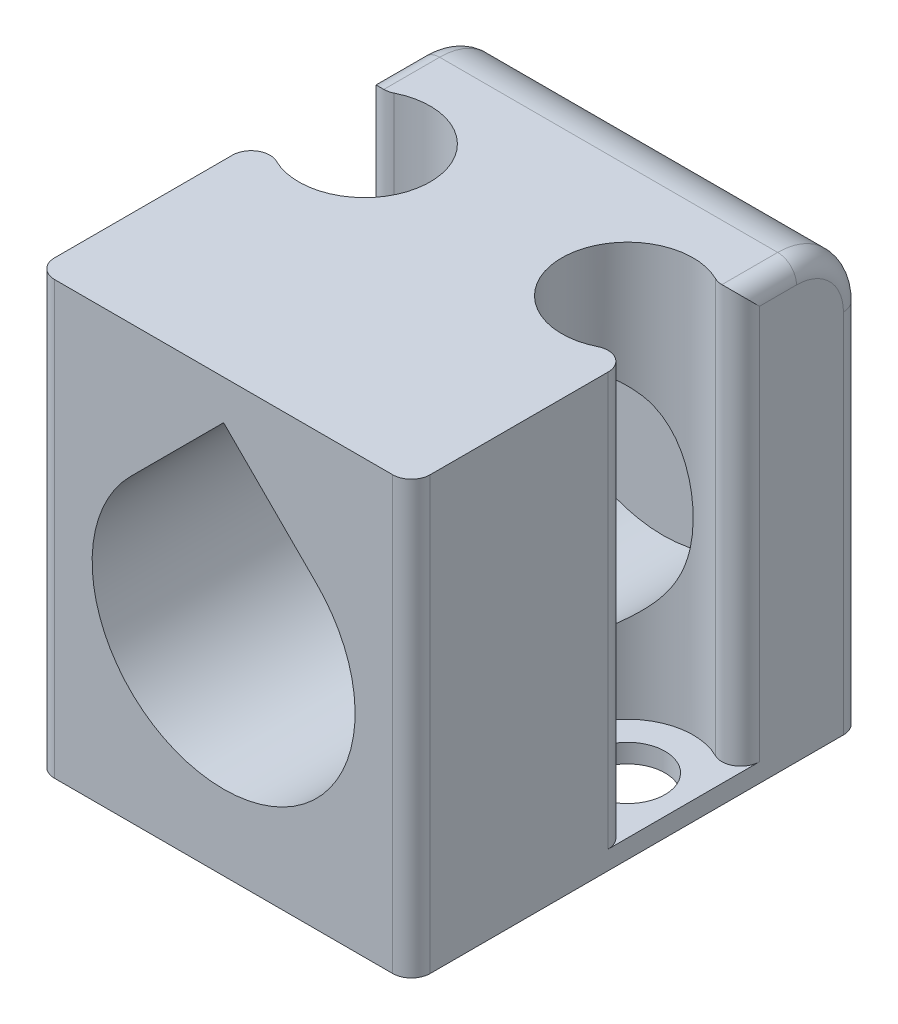
SolidWorks part; units mm, degrees
ref_plane "Front" through (0, 0, 0) normal (0, 0, 1) x (1, 0, 0)
ref_plane "Top" through (0, 0, 0) normal (0, 1, 0) x (1, 0, 0)
ref_plane "Right" through (0, 0, 0) normal (1, 0, 0) x (0, 0, -1)
other "Configuration Table"
sketch "Sketch1" plane through (0, 0, 0) normal (0, 1, 0) x (1, 0, 0)
  line L0 (0, 20.5519) -> (0, -18.8766) construction
  line L1 (-12.5093, 0) -> (15.4681, 0) construction
  line L2 (-10, 7.5) -> (10, 7.5)
  line L3 (-10, 7.5) -> (-10, -16.5)
  line L4 (-10, -16.5) -> (10, -16.5)
  line L5 (10, 7.5) -> (10, -16.5)
  circle A0 centre (-7, -2) radius 2
  circle A1 centre (7, -2) radius 2
  circle A2 centre (-7, -2) radius 3.5
  circle A3 centre (7, -2) radius 3.5
  dimension "D3" = 4
  dimension "D6" = 7
  dimension "D1" = 20
  dimension "D2" = 14
  dimension "D4" = 7.5
  dimension "D5" = 24
extrude "Boss-Extrude2" add sketch "Sketch1" along normal blind 1 contours A3 L5 L2 L3 A2 L4 | L3 A2 A0 | L5 A3 A1 region at (0, 0, 4.9595) region at (-6.0901, 0, -1.2806) region at (9.9045, 0, 2)
extrude "Boss-Extrude3" add sketch "Sketch1<4>" along normal blind 23 contours A3 L5 L2 L3 A2 L4 region at (0, 0, 4.9595)
sketch "Sketch1<4>" plane through (0, 0, 0) normal (0, 1, 0) x (1, 0, 0) same geometry as "Sketch1"
extrude "Boss-Extrude4" add sketch "Sketch1<5>" along normal blind 5 separate body contours A0 | L3 A2 A0 region at (-6.0901, 0, -1.2806) region at (-7, 0, 2)
sketch "Sketch1<5>" plane through (0, 0, 0) normal (0, 1, 0) x (1, 0, 0) same geometry as "Sketch1"
sketch "Sketch2" plane through (0, 0, 16.5) normal (0, 0, 1) x (1, 0, 0)
  line L1 (-4.9497, 15.9497) -> (0, 20.8995)
  line L2 (0, 20.8995) -> (4.9497, 15.9497)
  line L7 (-3.5, 0) -> (-10, 0)
  line L8 (-3.5, 0) -> (-10, 0) construction
  line L9 (-10, 0) -> (-10, 5)
  line L10 (-10, 0) -> (-10, 5) construction
  line L11 (-10, 5) -> (-3.5, 5)
  line L12 (-10, 5) -> (-3.5, 5) construction
  line L13 (-3.5, 5) -> (-3.5, 0)
  line L14 (-3.5, 5) -> (-3.5, 0) construction
  line L15 (-10, 0) -> (10, 0) construction
  arc A0 (-4.9497, 15.9497) -> (4.9497, 15.9497) centre (0, 11) ccw
  point P1 (0, 11.0236)
  point P8 (0, 0)
  point P9 (0, 19.3065)
  dimension "D1" = 14
  dimension "D2" = 4
extrude "Cut-Extrude1" cut sketch "Sketch2" against normal offset from surface (23.5 mm away) 0.5 up to face at (0, 11.5, -7.5)
delete or keep bodies "Body-Delete/Keep 1" type delete bodies bodies 106
fillet "Fillet2" radius 3.5 1 edges at (0, 23, -7.5)
fillet "Fillet1" radius 1 12 edges at (10, 12, 3.8028) (10, 12, 0.1972) (-10, 12, 3.8028) (-10, 12, 0.1972) (-10, 11.5, 16.5) (10, 11.5, 16.5) (10, 9.75, -7.5) (-10, 9.75, -7.5) (10, 23, -1.9014) (10, 21.9749, -6.4749) (-10, 23, -1.9014) (-10, 21.9749, -6.4749)
sketch "Sketch3" plane through (0, 0, -7) normal (0, 0, 1) x (1, 0, 0)
  line L0 (-9, 0) -> (-9, 19.5) construction
  line L1 (-8.9, 21) -> (8.9, 21)
  line L2 (-8.9, 21) -> (-8.9, 1)
  line L3 (-8.9, 1) -> (8.9, 1)
  line L4 (8.9, 21) -> (8.9, 1)
  line L5 (-8.9, 21) -> (8.9, 1) construction
  line L6 (-8.9, 1) -> (8.9, 21) construction
  line L7 (-3.5, 1) -> (-8.5556, 1) construction
  point P0 (0, 11)
  dimension "D1" = 0.1
extrude "Cut-Extrude2" [suppressed] cut sketch "Sketch3" along normal blind 0.1
sketch "Sketch4" plane through (0, 0, 0) normal (0, -1, 0) x (1, 0, 0)
  line L0 (-9.5, -2.2516) -> (-9.5, -6)
  line L1 (-8.5, -7) -> (8.5, -7)
  line L2 (9.5, -6) -> (9.5, -2)
  line L3 (0, 17.6401) -> (0, -15.3871) construction
  line L4 (7, -7) -> (-7, -7) construction
  line L5 (-9, -7.5) -> (9, -7.5) construction
  line L6 (-10, -6.5) -> (-10, 15.5) construction
  line L7 (-9.4, -2.2516) -> (-9.4, -6)
  line L8 (-8.5, -6.9) -> (8.5, -6.9)
  line L9 (9.4, -6) -> (9.4, -2)
  line L10 (-9.5, -2.2516) -> (-9.4, -2.2516)
  line L11 (9.5, -2) -> (9.4, -2)
  arc A0 (8.5, -7) -> (9.5, -6) centre (8.5, -6) ccw
  arc A1 (-9.5, -6) -> (-8.5, -7) centre (-8.5, -6) ccw
  arc A2 (-9.4, -6) -> (-8.5, -6.9) centre (-8.5, -6) ccw
  arc A3 (8.5, -6.9) -> (9.4, -6) centre (8.5, -6) ccw
  point P17 (9.5, -2.0152)
  dimension "D3" = 1
  dimension "D1" = 0.5
  dimension "D2" = 0.5
  dimension "D4" = 5
  dimension "D5" = 0.1
extrude "Cut-Extrude3" cut sketch "Sketch4" against normal up to vertex (19.5 mm away) from surface up to point (-10, 19.5, -6.5) starting at face at (-8.1385, 1, 2)
equation "\"D2@Sketch4\"=\"D1@Sketch4\""
